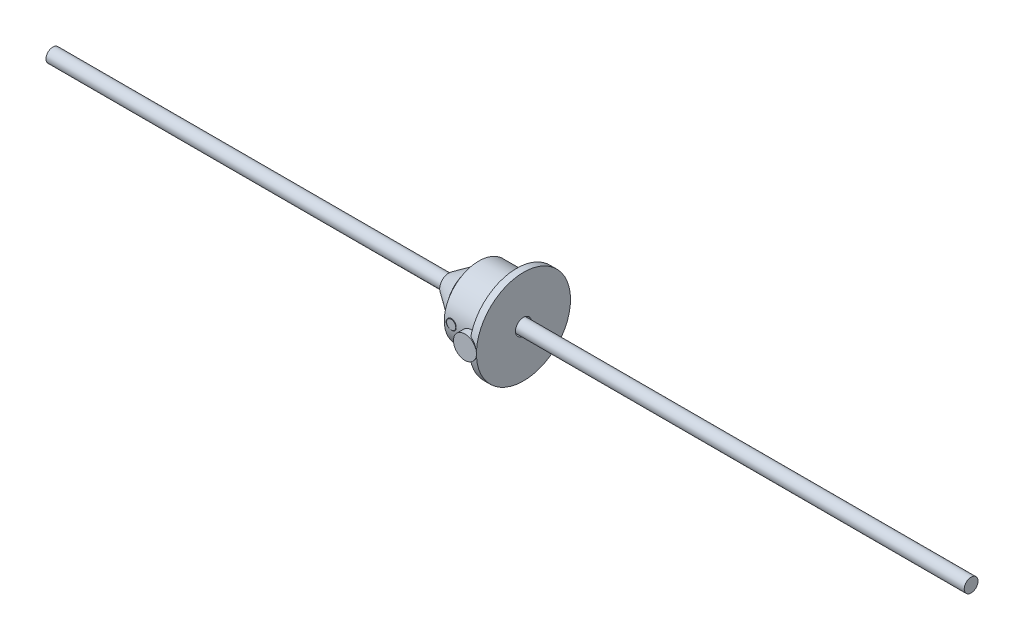
SolidWorks part; units mm, degrees
other "RD S Gear Inner"
other "RD S Gear Outer"
other "RD L Gear Left"
other "RD L Gear Right"
other "RD Ring Gear"
other "RD Pinion"
other "RD S Gear Inner"
ref_plane "Front Plane" through (0, 0, 0) normal (0, 0, 1) x (1, 0, 0)
ref_plane "Top Plane" through (0, 0, 0) normal (0, 1, 0) x (1, 0, 0)
ref_plane "Right Plane" through (0, 0, 0) normal (1, 0, 0) x (0, 0, -1)
sketch "Top View Layout" plane through (0, 0, 0) normal (0, 1, 0) x (1, 0, 0)
  line L0 (-100, 125) -> (100, 125)
  line L1 (0, 125) -> (0, -125)
  line L2 (-100, -125) -> (100, -125)
  line L3 (0, -15) -> (35, -15) construction
  line L4 (35, -15) -> (35, -125) construction
  line L5 (2.5, 114.75) -> (2.5, 135.25) construction
  line L6 (-2.5, 114.75) -> (2.5, 114.75) construction
  line L7 (-8.75, 127) -> (-2.75, 127) construction
  line L8 (-2.5, 114.75) -> (2.5, 114.75) construction
  line L9 (-2.5, 114.75) -> (-2.5, 116.25) construction
  line L10 (-2.5, 116.25) -> (2.5, 116.25) construction
  line L11 (2.5, 114.75) -> (2.5, 116.25) construction
  line L12 (2.5, 135.25) -> (1, 135.25) construction
  line L13 (2.5, 135.25) -> (2.5, 114.75) construction
  line L14 (2.5, 114.75) -> (1, 114.75) construction
  line L15 (1, 135.25) -> (1, 114.75) construction
  line L16 (-4.25, 128.5) -> (-2.75, 128.5) construction
  line L17 (-4.25, 128.5) -> (-4.25, 121.5) construction
  line L18 (-4.25, 121.5) -> (-2.75, 121.5) construction
  line L19 (-2.75, 128.5) -> (-2.75, 121.5) construction
  line L20 (-4.25, 128.5) -> (-2.75, 121.5) construction
  line L21 (-4.25, 121.5) -> (-2.75, 128.5) construction
  line L22 (-8.75, 128.5) -> (-7.25, 128.5) construction
  line L23 (-8.75, 128.5) -> (-8.75, 121.5) construction
  line L24 (-8.75, 121.5) -> (-7.25, 121.5) construction
  line L25 (-7.25, 128.5) -> (-7.25, 121.5) construction
  line L26 (-8.75, 128.5) -> (-7.25, 121.5) construction
  line L27 (-8.75, 121.5) -> (-7.25, 128.5) construction
  line L28 (-8.75, 123) -> (-2.75, 123) construction
  point P8 (0, 114.75)
  point P9 (0, 0)
  point P11 (2.5, 125)
  point P16 (2.5, 125)
  point P19 (0, 114.75)
  point P23 (-3.5, 125)
  point P28 (-8, 125)
  point P37 (0, 0)
  point P38 (0, 0)
  dimension "D1" = 250
  dimension "D2" = 200
  dimension "D3" = 35
  dimension "D4" = 15
  dimension "D5" = 5
  dimension "D6" = 20.5
  dimension "D7" = 1.5
  dimension "D8" = 1.5
  dimension "D9" = 1.5
  dimension "D10" = 7
  dimension "D11" = 3.5
  dimension "D12" = 8
  dimension "D13" = 1.5
  dimension "D14" = 1.5
ref_plane "Left" through (100, 0, 0) normal (-1, 0, 0) x (0, 0, 1)
ref_plane "Right" through (-100, 0, 0) normal (-1, 0, 0) x (0, 0, 1)
sketch "Left Wheels" plane through (100, 0, 0) normal (-1, 0, 0) x (0, 0, 1)
  circle A0 centre (125, 0) radius 25
  circle A1 centre (-125, 0) radius 25
  point P4 (0, 0)
  point P6 (0, 0)
  point P8 (0, 0)
  point P9 (0, 0)
  point P10 (0, 0)
  dimension "D1" = 50
  dimension "D2" = 50
sketch "Right Wheels" plane through (-100, 0, 0) normal (-1, 0, 0) x (0, 0, 1)
  circle A0 centre (-125, 0) radius 25 construction
  circle A1 centre (125, 0) radius 25 construction
  circle A2 centre (-125, 0) radius 25
  circle A3 centre (125, 0) radius 25
  point P6 (0, 0)
ref_plane "Rear Differential Pinion Plane" through (0, 0, -114.75) normal (0, 0, 1) x (1, 0, 0)
sketch "Rear Differential Pinion Profile" plane through (0, 0, -114.75) normal (0, 0, 1) x (1, 0, 0)
  circle A0 centre (0, 0) radius 2.5
ref_plane "Rear Differential Ring Gear Plane" through (2.5, 0, 0) normal (1, 0, 0) x (0, 0, -1)
ref_plane "Rear Axle" through (0, 0, -125) normal (0, 0, 1) x (1, 0, 0)
sketch "Rear Differential Ring Gear Profile" plane through (2.5, 0, 0) normal (1, 0, 0) x (0, 0, -1)
  line L0 (114.75, 0) -> (135.25, 0) construction
  circle A0 centre (125, 0) radius 10.25
extrude "Rear Differential Pinion" add sketch "Rear Differential Pinion Profile" against normal blind 1.5 contours A0
extrude "Rear Differential Ring Gear" add sketch "Rear Differential Ring Gear Profile" against normal blind 1.5 separate body contours A0
ref_plane "RD Inner L Gear Plane" through (-2.75, 0, 0) normal (1, 0, 0) x (0, 0, -1)
ref_plane "RD Outer L Gear Plane" through (-8.75, 0, 0) normal (1, 0, 0) x (0, 0, -1)
sketch "RD Inner L Gear Profile" plane through (-2.75, 0, 0) normal (1, 0, 0) x (0, 0, -1)
  circle A0 centre (125, 0) radius 3.5
  point P2 (0, 0)
sketch "RD Outer L Gear Profile" plane through (-8.75, 0, 0) normal (1, 0, 0) x (0, 0, -1)
  line L0 (128.5, 0) -> (121.5, 0) construction
  circle A0 centre (125, 0) radius 3.5
ref_plane "RD Inner S Gear Plane" through (0, 0, -121.5) normal (0, 0, 1) x (1, 0, 0)
ref_plane "RD Outer S Gear Plane" through (0, 0, -128.5) normal (0, 0, 1) x (1, 0, 0)
sketch "RD Inner S Gear Profile" plane through (0, 0, -121.5) normal (0, 0, 1) x (1, 0, 0)
  line L0 (-8.75, 0) -> (-7.25, 0) construction
  circle A0 centre (-5.75, 0) radius 3
  point P3 (0, 0)
sketch "RD Outer S Gear Profile" plane through (0, 0, -128.5) normal (0, 0, 1) x (1, 0, 0)
  line L0 (-8.75, 0) -> (-7.25, 0) construction
  circle A2 centre (-5.75, 0) radius 3
  point P2 (0, 0)
extrude "RD Outer L Gear Extrude" add sketch "RD Outer L Gear Profile" along normal blind 1.5 separate body contours A0
extrude "RD Inner L Gear Extrude" add sketch "RD Inner L Gear Profile" against normal blind 1.5 separate body contours A0
extrude "RD Outer S Gear Extrude" add sketch "RD Outer S Gear Profile" along normal blind 1.5 separate body contours A2
extrude "RD Inner S Gear Extrude" add sketch "RD Inner S Gear Profile" against normal blind 1.5 separate body contours A0
sketch "RD Ring Gear Case Profile" plane through (1, 0, 0) normal (-1, 0, 0) x (0, 0, 1)
  line L0 (-121.5, 3.2113) -> (-121.5, -3.2113)
  line L1 (-128.5, 3.2113) -> (-128.5, -3.2113)
  line L2 (-121.5, 6.6332) -> (-121.5, 3.2113) construction
  line L3 (-128.5, 6.6332) -> (-128.5, 3.2113) construction
  line L4 (-121.5, -3.2113) -> (-121.5, -6.6332) construction
  line L5 (-128.5, -3.2113) -> (-128.5, -6.6332) construction
  circle A0 centre (-125, 0) radius 7.5
  arc A1 (-121.5, 3.2113) -> (-128.5, 3.2113) centre (-125, 0) ccw
  arc A2 (-121.5, -3.2113) -> (-121.5, 3.2113) centre (-125, 0) ccw construction
  arc A3 (-128.5, 3.2113) -> (-128.5, -3.2113) centre (-125, 0) ccw construction
  arc A4 (-128.5, -3.2113) -> (-121.5, -3.2113) centre (-125, 0) ccw
  point P7 (-121.5, 0)
  dimension "D1" = 15
  dimension "D2" = 9.5
extrude "RD Ring Gear Case " add sketch "RD Ring Gear Case Profile" along normal blind 8.25
sketch "Sketch11" plane through (-7.25, 0, 0) normal (-1, 0, 0) x (0, 0, 1)
  circle A0 centre (-125, 0) radius 5.5
  circle A1 centre (-125, 0) radius 4.75
  arc A2 (-121.5, 3.2113) -> (-128.5, 3.2113) centre (-125, 0) ccw construction
  dimension "D1" = 11
extrude "Boss-Extrude8" add sketch "Sketch11" along normal up to vertex up to point (-8.75, 0, -128.5)
fillet "Fillet1" radius 2 1 edges at (-7.25, 0, -119.5)
sketch "Sketch12" plane through (0, 0, -125) normal (0, 0, 1) x (1, 0, 0)
  line L0 (-8.75, 0) -> (-13.75, 0) construction
  line L1 (-8.75, 0) -> (-7.25, 0) construction
  line L2 (-8.75, 0) -> (-7.25, 0) construction
  line L3 (-100, 0) -> (100, 0) construction
  line L4 (-100, 0) -> (100, 0) construction
  line L5 (-8.75, 5.5) -> (-8.75, -5.5) construction
  line L6 (-13.75, 0) -> (-13.75, 2)
  line L7 (-13.75, 2) -> (-8.75, 5.5)
  line L8 (-13.75, 0) -> (-8.75, 0)
  line L9 (-8.75, 0) -> (-8.75, 5.5)
  point P15 (-13.75, 1)
  dimension "D1" = 5
  dimension "D2" = 2
revolve "Revolve1" add sketch "Sketch12" angle 360 about L0
sketch "Sketch13" plane through (2.5, 0, 0) normal (1, 0, 0) x (0, 0, -1)
  circle A0 centre (125, 0) radius 1.75
  dimension "D1" = 3.5
extrude "Cut-Extrude1" cut sketch "Sketch13" against normal through all
sketch "Sketch14" plane through (0, 0, -121.5) normal (0, 0, 1) x (1, 0, 0)
  circle A0 centre (-5.75, 0) radius 1
  dimension "D1" = 2
extrude "Boss-Extrude9" add sketch "Sketch14" along normal blind 4
sketch "Sketch15" plane through (0, 0, -121.5) normal (0, 0, 1) x (1, 0, 0)
  circle A0 centre (-5.75, 0) radius 1.1
  dimension "D1" = 2.2
extrude "Cut-Extrude2" cut sketch "Sketch15" against normal through all both and the other way through all
extrude "Boss-Extrude10" add sketch "Sketch14<2>" against normal blind 4 from surface starting at face at (-2.75, 0, -128.5)
sketch "Sketch14<2>" plane through (0, 0, -121.5) normal (0, 0, 1) x (1, 0, 0) same geometry as "Sketch14"
sketch "Sketch16" plane through (-8.75, 0, 0) normal (-1, 0, 0) x (0, 0, 1)
  circle A0 centre (-125, 0) radius 1.5
  dimension "D1" = 3
extrude "Boss-Extrude11" add sketch "Sketch16" along normal up to vertex (91.25 mm away) up to point (-100, 0, -125)
sketch "Sketch17" plane through (-2.75, 0, 0) normal (1, 0, 0) x (0, 0, -1)
  circle A0 centre (125, 0) radius 1.5 construction
  circle A1 centre (125, 0) radius 1.5
extrude "Boss-Extrude12" add sketch "Sketch17" along normal up to vertex (102.75 mm away) up to point (100, 0, -125)
